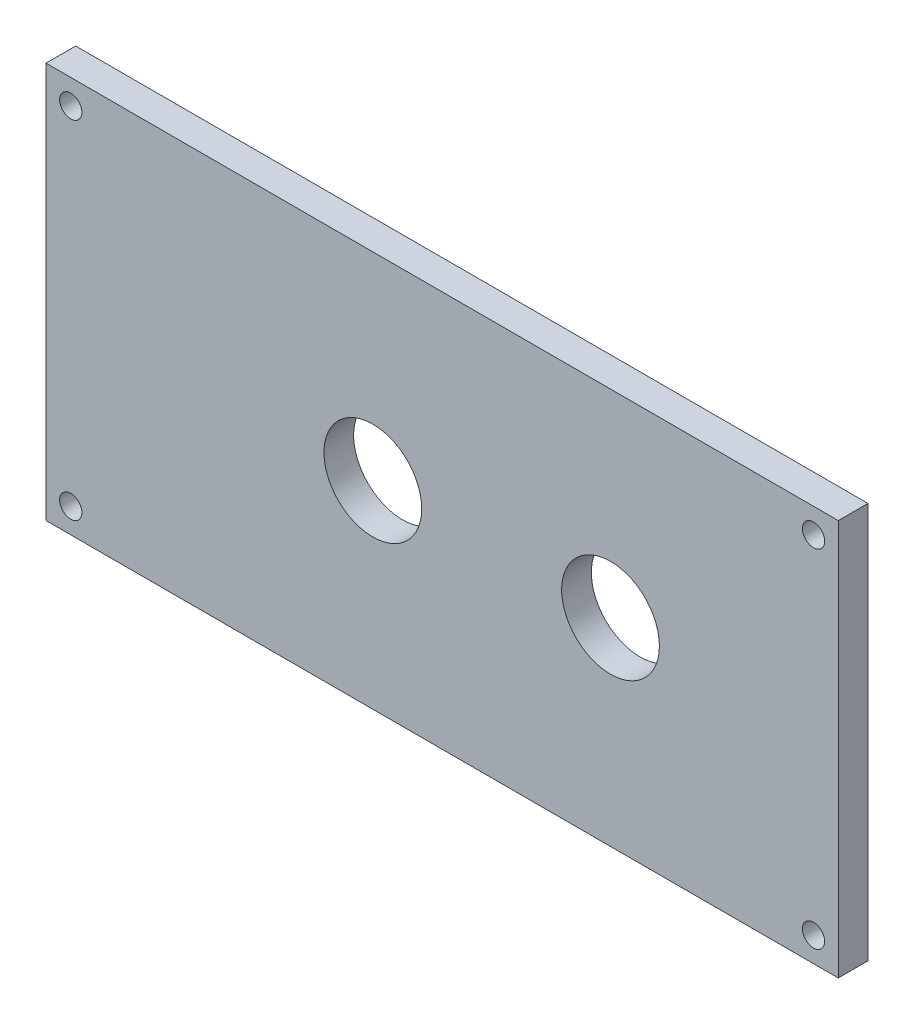
SolidWorks part; units mm, degrees
ref_plane "Front Plane" through (0, 0, 0) normal (0, 0, 1) x (1, 0, 0)
ref_plane "Top Plane" through (0, 0, 0) normal (0, 1, 0) x (1, 0, 0)
ref_plane "Right Plane" through (0, 0, 0) normal (1, 0, 0) x (0, 0, -1)
sketch "Sketch1" plane through (0, 0, 0) normal (0, 0, 1) x (1, 0, 0)
  line L1 (0, 0) -> (80, 0)
  line L2 (0, 0) -> (0, 40)
  line L3 (0, 40) -> (80, 40)
  line L4 (80, 0) -> (80, 40)
  dimension "D1" = 80
  dimension "D2" = 40
extrude "Boss-Extrude1" add sketch "Sketch1" along normal blind 3 contours L3 L4 L1 L2
sketch "Sketch2" plane through (0, 0, 3) normal (0, 0, 1) x (1, 0, 0)
  line L0 (0, 20) -> (80, 20) construction
  line L1 (0, 0) -> (0, 40) construction
  line L2 (80, 0) -> (80, 40) construction
  line L3 (0, 40) -> (80, 40) construction
  line L4 (40, 40) -> (40, 0) construction
  line L5 (0, 0) -> (80, 0) construction
  circle A1 centre (33, 20) radius 4.9365
  circle A2 centre (57, 20) radius 4.9365
  circle A3 centre (2.5, 37.5) radius 1.125
  circle A4 centre (77.5, 37.5) radius 1.125
  circle A5 centre (77.5, 2.5) radius 1.125
  circle A6 centre (2.5, 2.5) radius 1.125
  point P6 (0, 0)
  dimension "D1" = 33
  dimension "D2" = 9.873
  dimension "D3" = 9.873
  dimension "D7" = 2.25
  dimension "D6" = 24
  dimension "D8" = 2.5
  dimension "D9" = 2.5
extrude "Cut-Extrude1" cut sketch "Sketch2" against normal through all contours A3 | A6 | A1 | A2 | A4 | A5 region at (33, 20, 3) region at (57, 20, 3) region at (2.5, 37.5, 3) region at (77.5, 37.5, 3) region at (77.5, 2.5, 3) region at (2.5, 2.5, 3)
